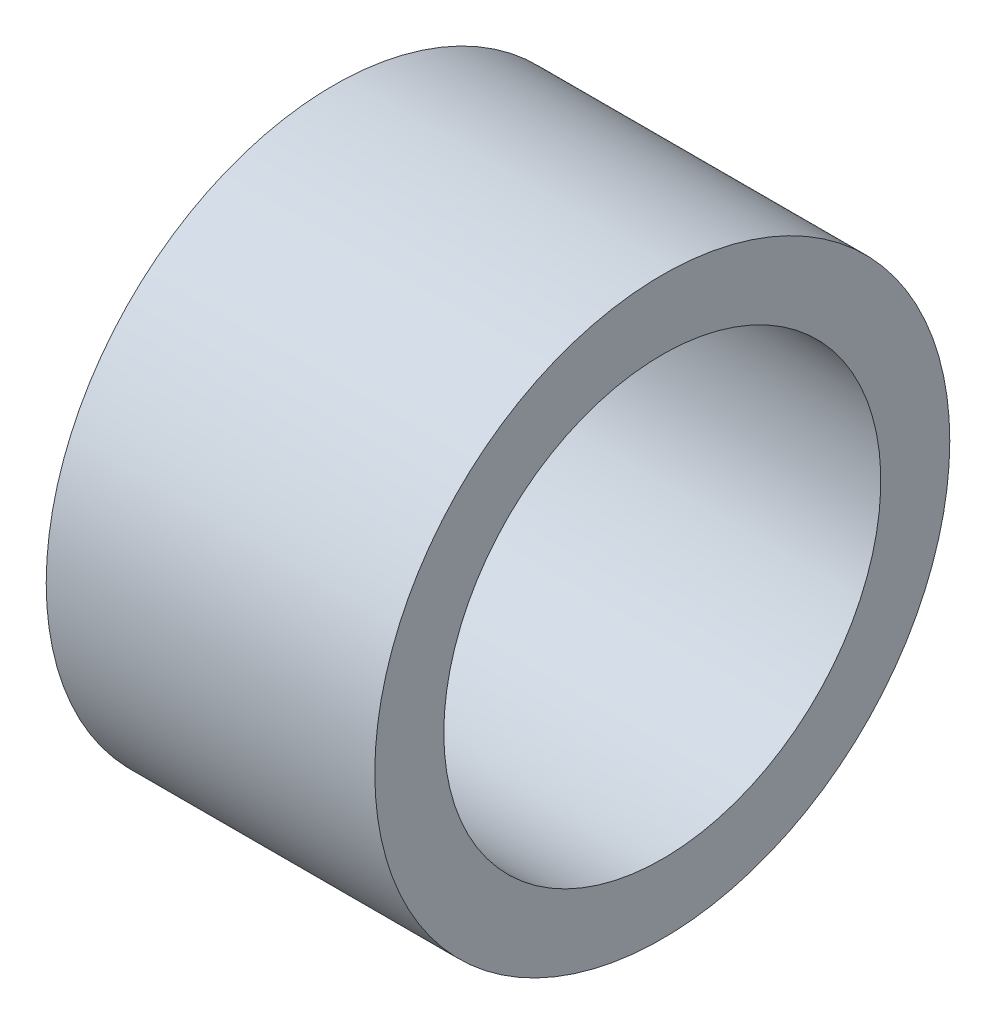
SolidWorks part; units mm, degrees
material "Nylon 6/10"
ref_plane "Front Plane" through (0, 0, 0) normal (0, 0, 1) x (1, 0, 0)
ref_plane "Top Plane" through (0, 0, 0) normal (0, 1, 0) x (1, 0, 0)
ref_plane "Right Plane" through (0, 0, 0) normal (1, 0, 0) x (0, 0, -1)
sketch "Sketch1" plane through (0, 0, 0) normal (0, 0, 1) x (1, 0, 0)
  line L0 (31.75, -11.935) -> (31.75, 10.1355) construction
  line L1 (31.75, 5.5563) -> (38.1, 5.5563)
  line L2 (31.75, 5.5563) -> (31.75, 4.2228)
  line L3 (31.75, 4.2228) -> (38.1, 4.2228)
  line L4 (38.1, 5.5563) -> (38.1, 4.2228)
  line L5 (0, 0) -> (42.6651, 0) construction
  line L7 (63.2354, 3.9688) -> (-48.4378, 3.9688) construction
  dimension "D1" = 0.254
  dimension "D2" = 11.1125
  dimension "D3" = 6.35
revolve "Revolve1" add sketch "Sketch1" angle 360 about L5
